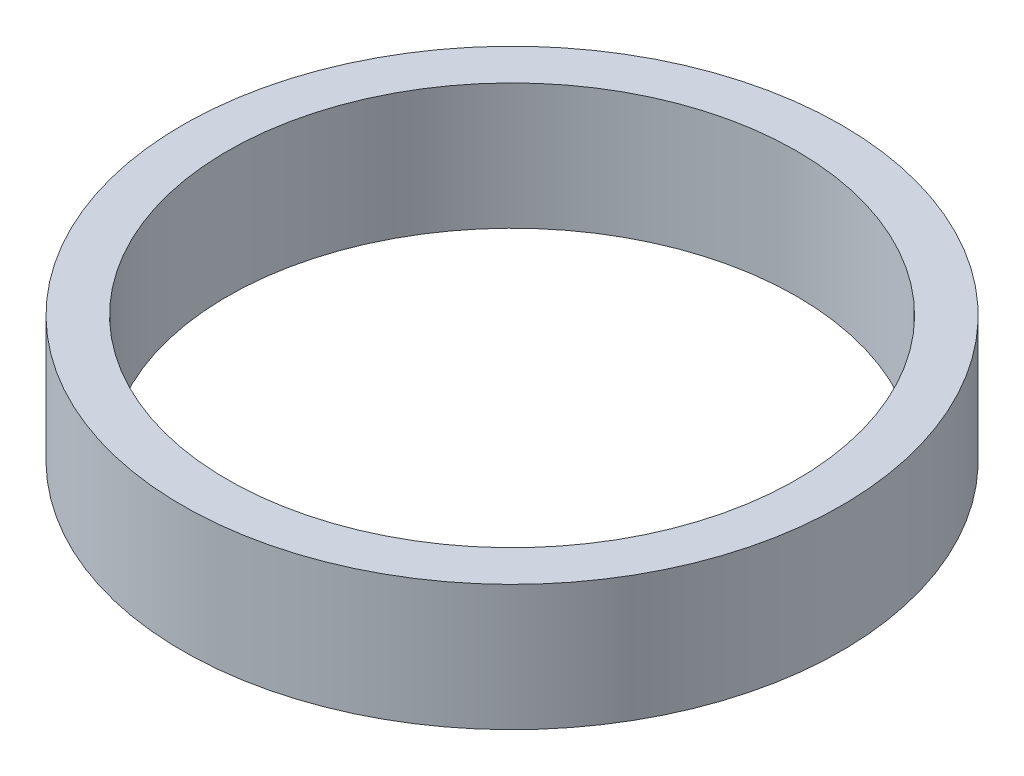
SolidWorks part; units mm, degrees
ref_plane "Front Plane" through (0, 0, 0) normal (0, 0, 1) x (1, 0, 0)
ref_plane "Top Plane" through (0, 0, 0) normal (0, 1, 0) x (1, 0, 0)
ref_plane "Right Plane" through (0, 0, 0) normal (1, 0, 0) x (0, 0, -1)
sketch "Sketch1" plane through (0, 0, 0) normal (0, 1, 0) x (1, 0, 0)
  circle A0 centre (0, 0) radius 55
  dimension "FLANGE_OD" = 110
extrude "Boss-Extrude1" add sketch "Sketch1" along normal blind 21
sketch "Sketch2" plane through (0, 0, 0) normal (0, 1, 0) x (1, 0, 0)
  circle A0 centre (0, 0) radius 47.5
  dimension "BORE_D" = 95
extrude "Cut-Extrude1" cut sketch "Sketch2" along normal through all
sketch "Sketch3" plane through (0, 21, 0) normal (0, 1, 0) x (1, 0, 0)
  circle A0 centre (0, 0) radius 25.4062 construction
  circle A1 centre (-25.4062, 0) radius 1.5
  dimension "BOLT_D" = 3
  dimension "BOLT_PCD" = 50.8124
extrude "Cut-Extrude2" cut sketch "Sketch3" against normal blind 17.4027 rebuild error yes
pattern_circular "CirPattern1" count 4 over 360 rebuild error yes
